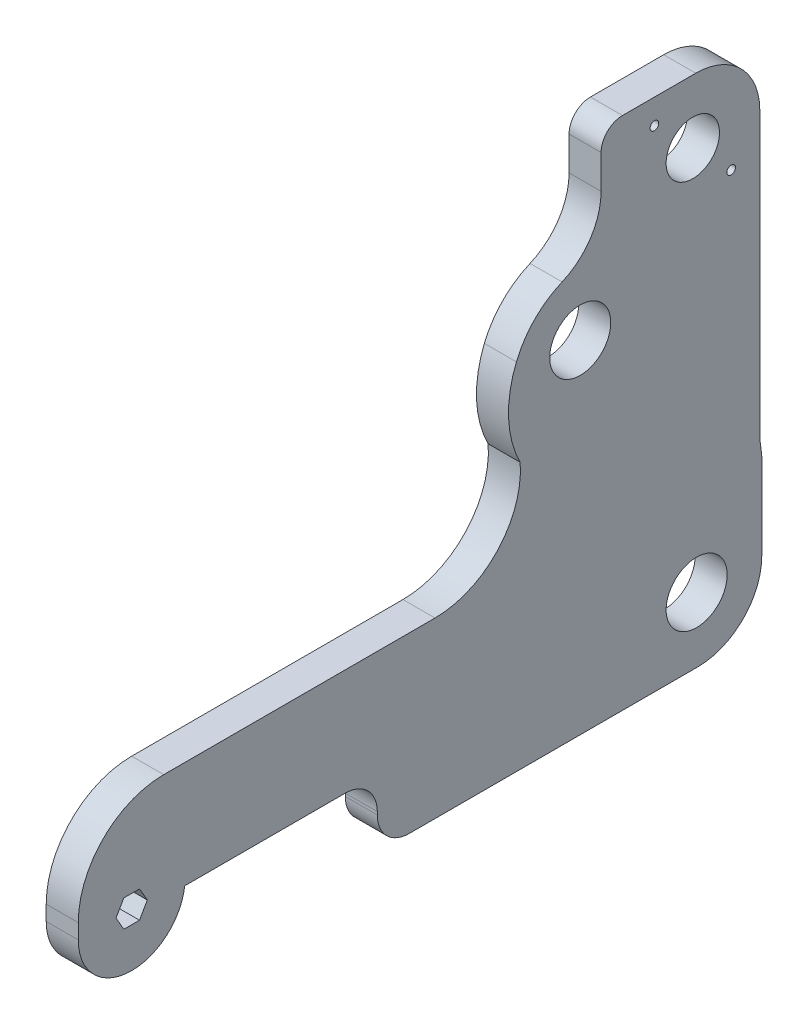
SolidWorks part; units mm, degrees
material "Cedro"
ref_plane "Alzado" through (0, 0, 0) normal (0, 0, 1) x (1, 0, 0)
ref_plane "Planta" through (0, 0, 0) normal (0, 1, 0) x (1, 0, 0)
ref_plane "Vista lateral" through (0, 0, 0) normal (1, 0, 0) x (0, 0, -1)
sketch "Croquis1" plane through (0, 0, 0) normal (1, 0, 0) x (0, 0, -1)
  line L0 (65, 25.4) -> (65, 281.0616)
  line L1 (65, 281.0616) -> (385, 281.0616)
  line L2 (385, 281.0616) -> (385, -8.9384)
  line L5 (115, 22.4) -> (205, 22.4)
  line L6 (205, 22.4) -> (205, -8.9384)
  line L7 (205, -8.9384) -> (385, -8.9384)
  line L8 (65, 25.4) -> (115, 25.4) construction
  line L9 (115, 25.4) -> (90, 25.4) construction
  line L10 (90, 25.4) -> (90, 0) construction
  line L11 (115, 22.4) -> (114.8193, 22.4)
  line L12 (82.6677, 25.4) -> (86.3338, 19.05)
  line L13 (86.3338, 19.05) -> (93.6662, 19.05)
  line L14 (93.6662, 19.05) -> (97.3323, 25.4)
  line L15 (97.3323, 25.4) -> (93.6662, 31.75)
  line L16 (93.6662, 31.75) -> (86.3338, 31.75)
  line L17 (86.3338, 31.75) -> (82.6677, 25.4)
  arc A0 (65, 25.4) -> (114.8193, 22.4) centre (90, 25.4) ccw
  circle A1 centre (90, 25.4) radius 6.35 construction
  dimension "D4" = 25
  dimension "D1" = 12.7
  dimension "D2" = 180
  dimension "D3" = 290
  dimension "D5" = 90
  dimension "D6" = 3
  dimension "D7" = 25.4
  dimension "D8" = 255.6616
extrude "Saliente-Extruir1" add sketch "Croquis1" along normal blind 15 contours L0 L1 L2 L7 L6 L5 L11 A0
sketch "Croquis2" plane through (0, 0, 0) normal (-1, 0, 0) x (0, 0, 1)
  line L1 (-82.6677, 25.4) -> (-86.3338, 31.75)
  line L2 (-86.3338, 31.75) -> (-93.6662, 31.75)
  line L3 (-93.6662, 31.75) -> (-97.3323, 25.4)
  line L4 (-97.3323, 25.4) -> (-93.6662, 19.05)
  line L5 (-93.6662, 19.05) -> (-86.3338, 19.05)
  line L6 (-86.3338, 19.05) -> (-82.6677, 25.4)
  circle A0 centre (-90, 25.4) radius 6.35 construction
  dimension "D1" = 12.7
extrude "Cortar-Extruir1" cut sketch "Croquis2" against normal through all
fillet "Redondeo1" radius 220 1 edges at (7.5, 281.0616, -385)
fillet "Redondeo2" radius 70 1 edges at (7.5, 281.0616, -65)
fillet "Redondeo3" radius 15 2 edges at (7.5, 22.4, -205) (7.5, -8.9384, -205)
fillet "Redondeo4" radius 30 1 edges at (7.5, -8.9384, -385)
sketch "Croquis7" plane through (15, 0, 0) normal (1, 0, 0) x (0, 0, -1)
  circle A0 centre (354.5, 21.5616) radius 14.29
extrude "Cortar-Extruir5" cut sketch "Croquis7" against normal through all
sketch "Croquis8" plane through (15, 0, 0) normal (1, 0, 0) x (0, 0, -1)
  circle A0 centre (300, 151.0616) radius 14.29
extrude "Cortar-Extruir6" cut sketch "Croquis8" against normal blind 523
sketch "Croquis14" plane through (15, 0, 0) normal (1, 0, 0) x (0, 0, -1)
  line L0 (65, 72.4) -> (270, 72.4)
  line L1 (65, 25.4) -> (65, 211.0616) construction
  line L2 (190, 22.4) -> (114.8193, 22.4) construction
  line L3 (65, 72.4) -> (0, 212.5831)
  line L4 (0, 212.5831) -> (105.3354, 302.0886)
  line L5 (105.3354, 302.0886) -> (409.0379, 257.3358)
  line L6 (409.0379, 257.3358) -> (360.9592, 161.0616)
  arc A0 (270, 72.4) -> (271.8868, 115.6071) centre (204.4306, 96.9081) ccw
  arc A1 (271.8868, 115.6071) -> (360.9592, 161.0616) centre (316.423, 138.3344) cw
  arc A2 (385, 61.0616) -> (165, 281.0616) centre (165, 61.0616) ccw construction
  dimension "D4" = 50
  dimension "D5" = 70
  dimension "D1" = 50
  dimension "D2" = 205
  dimension "D3" = 120
  dimension "D6" = 100
extrude "Cortar-Extruir12" cut sketch "Croquis14" against normal through all
fillet "Redondeo5" radius 40 2 edges at (7.5, 72.4, -270) (7.5, 72.4, -65)
sketch "Croquis15" plane through (15, 0, 0) normal (1, 0, 0) x (0, 0, -1)
  line L0 (316.423, 188.3344) -> (358.6262, 190.9225)
  line L1 (358.6262, 190.9225) -> (422.7612, 101.2041)
  line L2 (422.7612, 101.2041) -> (385, 21.0616)
  arc A0 (385, 21.0616) -> (316.423, 188.3344) centre (196.0814, 41.3041) ccw
  arc A1 (360.9592, 161.0616) -> (271.8868, 115.6071) centre (316.423, 138.3344) ccw construction
  dimension "D1" = 190
extrude "Cortar-Extruir13" cut sketch "Croquis15" against normal through all
fillet "Redondeo6" radius 40 1 edges at (7.5, 188.3344, -316.423)
sketch "Croquis18" plane through (0, 0, 0) normal (-1, 0, 0) x (0, 0, 1)
  line L0 (-336.7832, 168.9873) -> (-324.9259, 170.9541)
  line L1 (-324.9259, 170.9541) -> (-309.7802, 182.0208)
  arc A0 (-336.7832, 168.9873) -> (-309.7802, 182.0208) centre (-323.0682, 175.0617) cw
  dimension "D1" = 15
  dimension "D4" = 29.9839
extrude "Saliente-Extruir3" add sketch "Croquis18" against normal through all
sketch "Croquis20" plane through (0, 0, 0) normal (-1, 0, 0) x (0, 0, 1)
  line L2 (-384.0804, 202.2548) -> (-384.0804, 68.8062)
  line L3 (-384.0804, 68.8062) -> (-355.9557, 128.1982)
  line L4 (-355.9557, 128.1982) -> (-350.9889, 138.6868)
  line L5 (-350.9889, 138.6868) -> (-333.3915, 167.9022)
  line L6 (-333.3915, 167.9022) -> (-333.3915, 179.1455)
  line L7 (-333.3915, 179.1455) -> (-331.8486, 185.409)
  line L8 (-331.8486, 185.409) -> (-327.7227, 187.904)
  line L9 (-327.7227, 187.904) -> (-321.4656, 187.904)
  line L10 (-321.4656, 187.904) -> (-315.2356, 184.1515)
  line L11 (-315.2356, 184.1515) -> (-309.7802, 182.0208)
  line L12 (-354.0804, 232.2548) -> (-319.7802, 232.2548)
  line L13 (-309.7802, 182.0208) -> (-309.7802, 222.2548)
  arc A2 (-354.0804, 232.2548) -> (-384.0804, 202.2548) centre (-354.0804, 202.2548) ccw
  arc A3 (-319.7802, 232.2548) -> (-309.7802, 222.2548) centre (-319.7802, 222.2548) cw
extrude "Saliente-Extruir4" add sketch "Croquis20" against normal through all
sketch "Croquis21" plane through (0, 0, 0) normal (-1, 0, 0) x (0, 0, 1)
  circle A0 centre (-334.745, 220.6292) radius 2.02
  circle A1 centre (-370.666, 184.7082) radius 2.02
  circle A2 centre (-352.7055, 202.6687) radius 12.5
  dimension "D1" = 25
  dimension "D2" = 4.04
  dimension "D3" = 4.04
extrude "Cortar-Extruir17" cut sketch "Croquis21" against normal through all
fillet "Redondeo7" radius 30 1 edges at (7.5, 182.0208, -309.7802)
